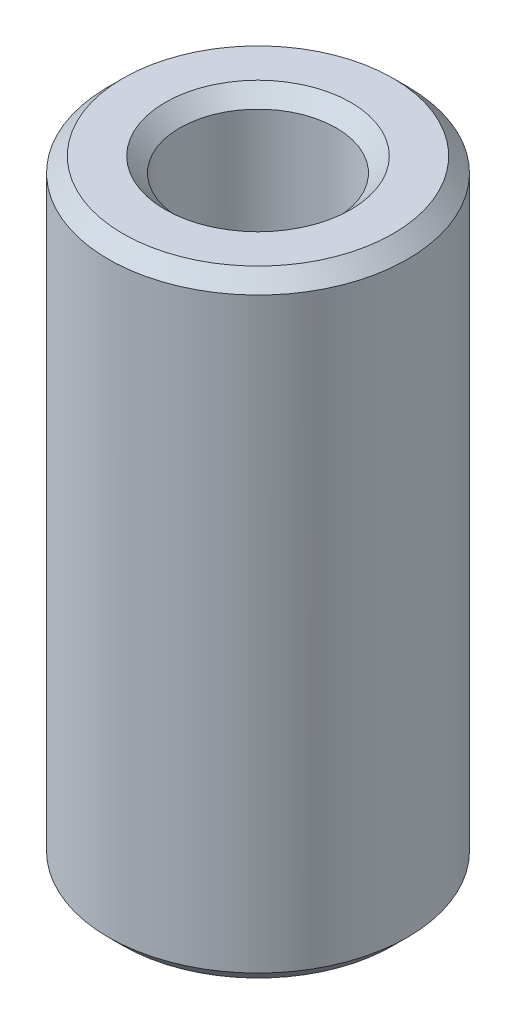
SolidWorks part; units mm, degrees
ref_plane "Front Plane" through (0, 0, 0) normal (0, 0, 1) x (1, 0, 0)
ref_plane "Top Plane" through (0, 0, 0) normal (0, 1, 0) x (1, 0, 0)
ref_plane "Right Plane" through (0, 0, 0) normal (1, 0, 0) x (0, 0, -1)
sketch "Sketch1" plane through (0, 0, 0) normal (0, 1, 0) x (1, 0, 0)
  circle A0 centre (0, 0) radius 27.5
  dimension "SLEEVE_OD" = 55
extrude "Boss-Extrude1" add sketch "Sketch1" along normal blind 113.3772
sketch "Sketch2" plane through (0, 0, 0) normal (0, 1, 0) x (1, 0, 0)
  circle A0 centre (0, 0) radius 14.3723
  dimension "BORE_D" = 28.7446
extrude "Cut-Extrude1" cut sketch "Sketch2" along normal through all
chamfer "Chamfer1" distance 2.7013 angle 45 4 edges at (0, 113.3772, 14.3723) (0, 0, 14.3723) (0, 0, 27.5) (0, 113.3772, 27.5)
